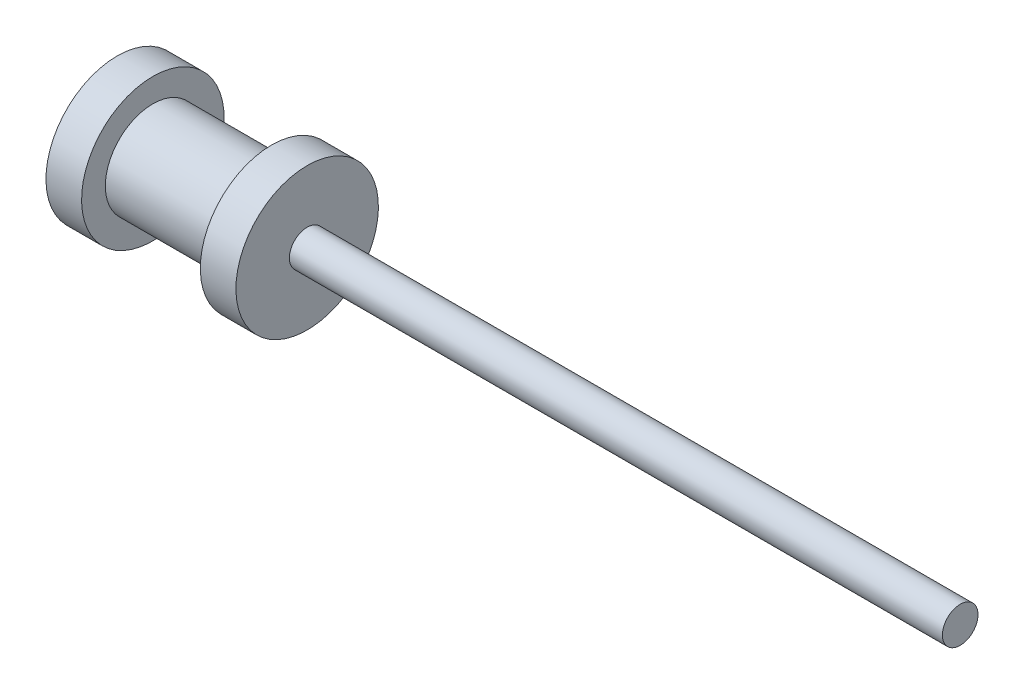
SolidWorks part; units mm, degrees
ref_plane "Front Plane" through (0, 0, 0) normal (0, 0, 1) x (1, 0, 0)
ref_plane "Top Plane" through (0, 0, 0) normal (0, 1, 0) x (1, 0, 0)
ref_plane "Right Plane" through (0, 0, 0) normal (1, 0, 0) x (0, 0, -1)
sketch "Sketch1" plane through (0, 0, 0) normal (0, 0, 1) x (1, 0, 0)
  line L0 (0, 0) -> (0, -6)
  line L1 (0, -6) -> (3, -6)
  line L2 (3, -6) -> (3, -4)
  line L3 (3, -4) -> (13, -4)
  line L4 (13, -4) -> (13, -6)
  line L5 (13, -6) -> (16, -6)
  line L6 (16, -6) -> (16, -1.5)
  line L7 (16, -1.5) -> (71, -1.5)
  line L8 (71, -1.5) -> (71, 0)
  line L9 (71, 0) -> (0, 0)
  dimension "D1" = 3
  dimension "D2" = 3
  dimension "D3" = 10
  dimension "D4" = 55
  dimension "D5" = 1.5
  dimension "D6" = 6
  dimension "D7" = 4
revolve "Revolve1" add sketch "Sketch1" angle 360 about L9
